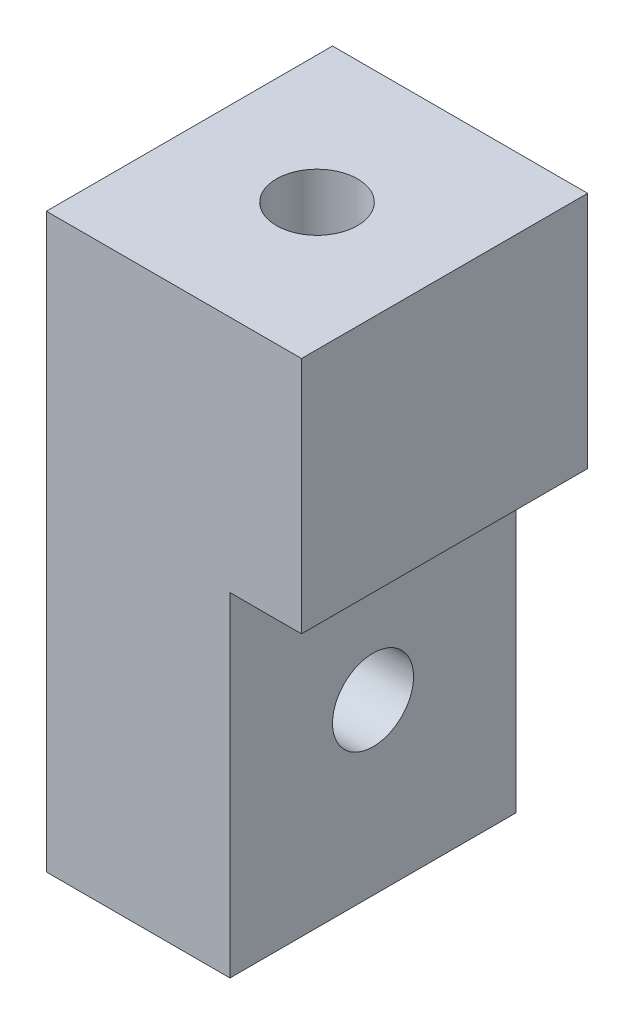
SolidWorks part; units mm, degrees
ref_plane "Front Plane" through (0, 0, 0) normal (0, 0, 1) x (1, 0, 0)
ref_plane "Top Plane" through (0, 0, 0) normal (0, 1, 0) x (1, 0, 0)
ref_plane "Right Plane" through (0, 0, 0) normal (1, 0, 0) x (0, 0, -1)
sketch "Sketch1" plane through (0, 0, 0) normal (0, 0, 1) x (1, 0, 0)
  line L0 (1.175, -6) -> (1.175, 1)
  line L1 (-2.675, 6) -> (2.675, 6)
  line L2 (-2.675, 6) -> (-2.675, -6)
  line L3 (-2.675, -6) -> (2.675, -6)
  line L4 (2.675, 6) -> (2.675, -6)
  line L5 (-2.675, 6) -> (2.675, -6) construction
  line L6 (-2.675, -6) -> (2.675, 6) construction
  line L7 (1.175, 1) -> (2.675, 1)
  line L8 (2.675, 1) -> (2.675, -6)
  point P0 (0, 0)
  dimension "D1" = 0
  dimension "D2" = 12
  dimension "D3" = 1.5
  dimension "D4" = 3.85
  dimension "D5" = 5.35
  dimension "D6" = 5
extrude "Boss-Extrude1" add sketch "Sketch1" along normal blind 6 contours L7 L8 L3 L4 L1 L2 L0 region at (-0.3764, 0.4888, 0)
sketch "Sketch2" plane through (-2.675, 0, 0) normal (-1, 0, 0) x (0, 0, 1)
  line L0 (3, 1.1) -> (3, -6) construction
  line L1 (6, 6) -> (0, 6) construction
  line L2 (6, -2.45) -> (0, -2.45) construction
  line L3 (0, 6) -> (0, -6) construction
  line L5 (6, -6) -> (0, -6)
  line L6 (6, -6) -> (6, 1.1)
  line L7 (6, 1.1) -> (0, 1.1)
  line L8 (0, -6) -> (0, 1.1)
  circle A0 centre (3, -2.45) radius 0.85
  dimension "D1" = 1.7
  dimension "D3" = 8.45
  dimension "D2" = 3.55
extrude "Cut-Extrude1" cut sketch "Sketch2" against normal through all contours A0
sketch "Sketch3" plane through (0, 6, 0) normal (0, 1, 0) x (1, 0, 0)
  line L0 (2.675, -6) -> (2.675, 0) construction
  line L1 (1.025, -6) -> (1.025, 0) construction
  line L2 (-2.675, -6) -> (2.675, -6) construction
  line L3 (-2.675, -3) -> (2.675, -3) construction
  line L4 (-2.675, -6) -> (-2.675, 0) construction
  line L5 (2.675, -6) -> (-0.625, -6) construction
  line L6 (-2.675, 0) -> (2.675, 0) construction
  line L7 (0, 0) -> (0, -6) construction
  circle A0 centre (0, -3) radius 0.85
  dimension "D1" = 1.7
  dimension "D2" = 3.3
extrude "Cut-Extrude2" cut sketch "Sketch3" against normal up to surface (5 mm away) up to face at (1.925, 1, 3)
